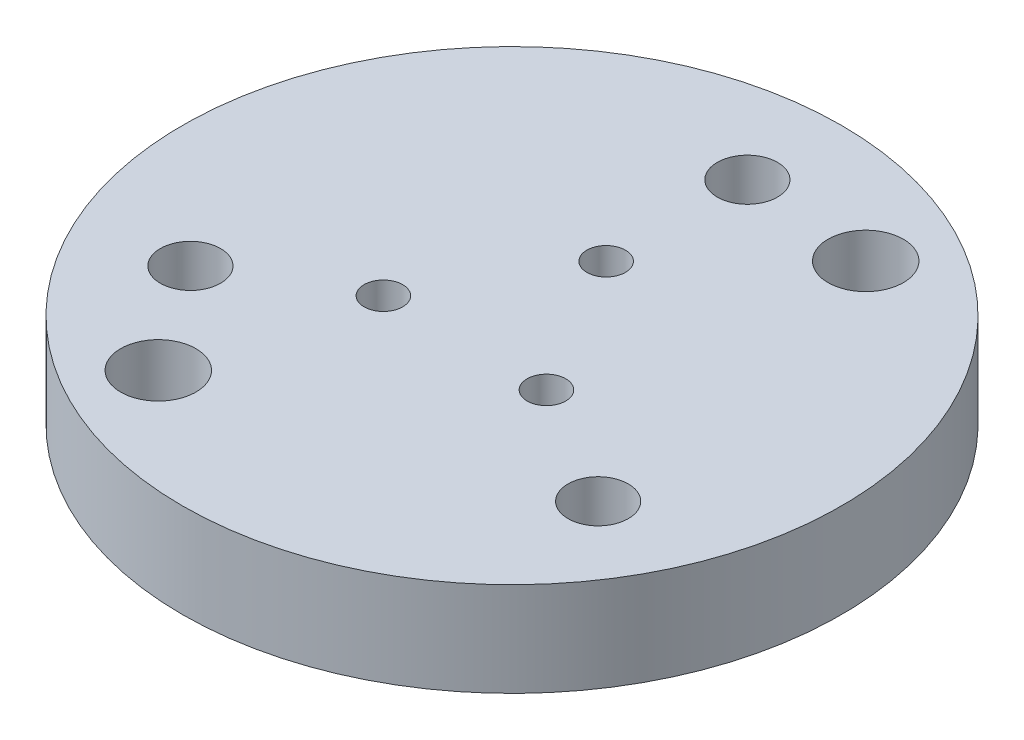
SolidWorks part; units mm, degrees
material "K110"
ref_plane "Front Plane" through (0, 0, 0) normal (0, 0, 1) x (1, 0, 0)
ref_plane "Top Plane" through (0, 0, 0) normal (0, 1, 0) x (1, 0, 0)
ref_plane "Right Plane" through (0, 0, 0) normal (1, 0, 0) x (0, 0, -1)
sketch "Sketch1" plane through (0, 0, 0) normal (0, 1, 0) x (1, 0, 0)
  circle A0 centre (0, 0) radius 35
  dimension "D1" = 70
extrude "Boss-Extrude1" add sketch "Sketch1" against normal blind 10
sketch "Sketch2" plane through (0, 0, 0) normal (0, 1, 0) x (1, 0, 0)
  circle A0 centre (8.6603, -5) radius 2.05 construction
  circle A1 centre (0, 10) radius 2.05 construction
  circle A2 centre (-8.6603, -5) radius 2.05 construction
  circle A3 centre (8.6603, -5) radius 2.05
  circle A4 centre (0, 10) radius 2.05
  circle A5 centre (-8.6603, -5) radius 2.05
extrude "Cut-Extrude1" cut sketch "Sketch2" against normal up to next
hole_wizard "Ø8.0mm Dowel Hole1" positions "Sketch5" profile "Sketch4" hole size "Ø8.0" standard "ISO" end condition through all
sketch "Sketch5" plane through (0, -10, 0) normal (0, -1, 0) x (-1, 0, 0)
  point P0 (-13.75, 23.8157)
  point P3 (13.75, -23.8157)
sketch "Sketch4" plane through (13.75, -10, -23.8157) normal (1, 0, 0) x (0, 0, -1)
  line L0 (0, 0) -> (0, 10)
  line L1 (0, 10) -> (4, 10)
  line L2 (4, 10) -> (4, 0)
  line L5 (4, 0) -> (0, 0)
  line L11 (0, -6.35) -> (0, 107.95) construction
  dimension "Thru Hole Dia." = 8
  dimension "Thru Hole Depth" = 10
hole_wizard "M6 Clearance Hole1" positions "Sketch9" profile "Sketch7" hole size "M6" standard "ISO" end condition through all
sketch "Sketch9" plane through (0, -10, 0) normal (0, -1, 0) x (-1, 0, 0)
  point P0 (-21.6506, -12.5)
  point P3 (21.6506, -12.5)
  point P7 (0, 25)
sketch "Sketch7" plane through (21.6506, -10, 12.5) normal (1, 0, 0) x (0, 0, -1)
  line L0 (0, 0) -> (0, 10)
  line L1 (0, 10) -> (3.2, 10)
  line L2 (3.2, 10) -> (3.2, 0)
  line L5 (3.2, 0) -> (0, 0)
  line L11 (0, -6.35) -> (0, 107.95) construction
  dimension "Thru Hole Dia." = 6.4
  dimension "Thru Hole Depth" = 10
